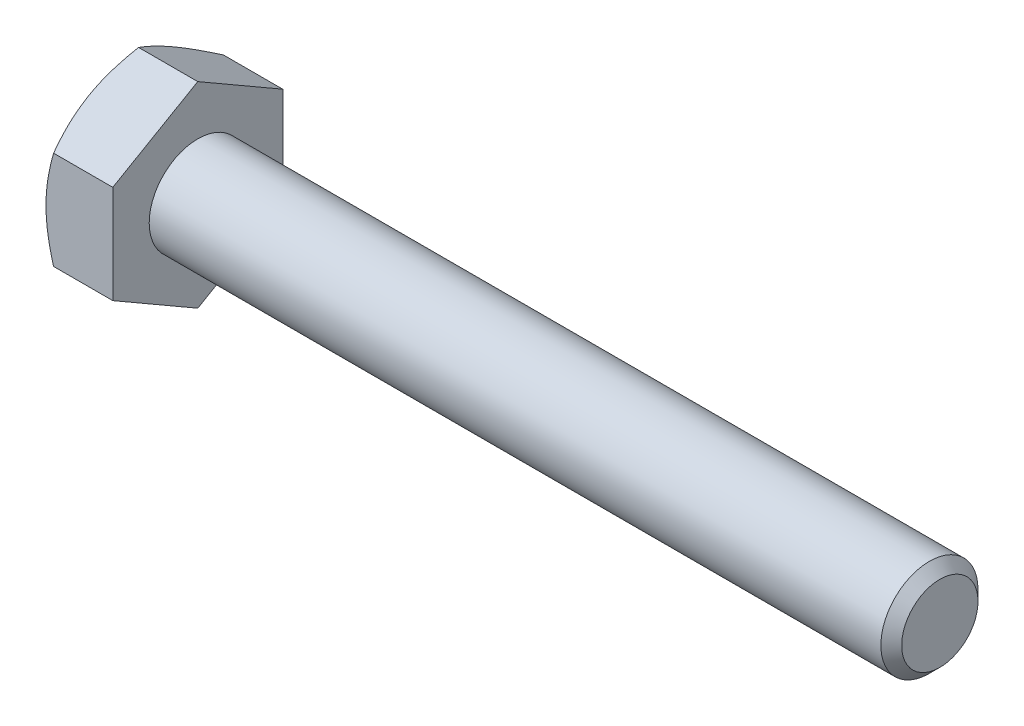
SolidWorks part; units mm, degrees
material "Alloy Steel"
ref_plane "Front Plane" through (0, 0, 0) normal (0, 0, 1) x (1, 0, 0)
ref_plane "Top Plane" through (0, 0, 0) normal (0, 1, 0) x (1, 0, 0)
ref_plane "Right Plane" through (0, 0, 0) normal (1, 0, 0) x (0, 0, -1)
sketch "Sketch1" plane through (0, 0, 0) normal (0, 0, 1) x (1, 0, 0)
  line L0 (-26.4398, 0) -> (26.4398, 0) construction
  line L1 (26.4398, 3.175) -> (26.4398, -3.175) construction
  line L2 (-22.0742, 5.5562) -> (-22.0742, -5.5562) construction
  line L3 (-26.4398, 5.5562) -> (-26.4398, -5.5562) construction
  point P9 (-22.0742, 0)
  point P10 (23.2648, -3.175)
  dimension "Screw Dia" = 6.35
  dimension "Hex" = 11.1125
  dimension "Head Ht" = 4.3656
  dimension "Screw Lenght" = 48.514
  dimension "D1" = 3.175
ref_plane "Plane2" through (26.4398, 0, 0) normal (1, 0, 0) x (0, 0, -1)
sketch "Sketch5" plane through (26.4398, 0, 0) normal (1, 0, 0) x (0, 0, -1)
  circle A0 centre (0, 0) radius 3.175
extrude "Boss-Extrude3" add sketch "Sketch5" against normal up to vertex (48.514 mm away) up to point (-22.0742, 0, 0)
sketch "Sketch9" plane through (26.4398, 0, 0) normal (1, 0, 0) x (0, 0, -1)
  circle A1 centre (0, 0) radius 3.175
  circle A2 centre (0, 0) radius 3.175
  dimension "D1" = 0
curve "Helix/Spiral1" [suppressed] pitch 0.9071 height 19.9571 turns 22 parameters "Pitch"=0.9071
chamfer "Chamfer1" distance 0.6804 angle 45 1 edges at (26.4398, 0, -3.175)
sketch "Sketch10" plane through (0, 0, 0) normal (0, 0, 1) x (1, 0, 0)
  line L0 (26.4398, 3.175) -> (26.78, 2.5858)
  line L1 (26.78, 2.5858) -> (26.8934, 2.5858)
  line L2 (26.8934, 2.5858) -> (27.2336, 3.175)
  line L3 (26.4398, 3.175) -> (27.2336, 3.175)
  line L4 (26.8367, 3.175) -> (26.8367, 2.5858) construction
  line L5 (26.6099, 2.8804) -> (27.0635, 2.8804) construction
  dimension "D1" = 60
  dimension "D2" = 0.1134
  dimension "D3" = 0.4536
sweep "Cut-Sweep1" [suppressed] cut profiles "Sketch10" path "Helix/Spiral1"
sketch "Sketch11" plane through (0, 0, 0) normal (0, 0, 1) x (1, 0, 0)
  line L0 (-22.0742, 3.175) -> (-22.0742, 0)
  line L1 (-22.0742, 0) -> (10.5648, 0)
  line L3 (10.5648, 0) -> (7.3898, 3.175)
  line L4 (-22.0742, 3.175) -> (7.3898, 3.175)
  dimension "D1" = 45
  dimension "MIn Thread" = 19.05
revolve "Revolve1" [suppressed] add sketch "Sketch11" angle 360 about L1
sketch "Sketch6" plane through (-22.0742, 0, 0) normal (-1, 0, 0) x (0, 0, 1)
  line L0 (0, 5.5562) -> (0, -5.5562) construction
  line L1 (5.5562, 3.2079) -> (0, 6.4158)
  line L2 (0, 6.4158) -> (-5.5562, 3.2079)
  line L3 (-5.5562, 3.2079) -> (-5.5562, -3.2079)
  line L4 (-5.5562, -3.2079) -> (0, -6.4158)
  line L5 (0, -6.4158) -> (5.5563, -3.2079)
  line L6 (5.5563, -3.2079) -> (5.5562, 3.2079)
  circle A0 centre (0, 0) radius 5.5562 construction
extrude "Boss-Extrude4" add sketch "Sketch6" along normal up to vertex (4.3656 mm away) up to point (-26.4398, -5.5562, 0)
sketch "Sketch7" plane through (-26.4398, 0, 0) normal (-1, 0, 0) x (0, 0, 1)
  circle A0 centre (0, 0) radius 5.5562 construction
  circle A1 centre (0, 0) radius 5.5562
sketch "Sketch8" plane through (-26.4398, 0, 0) normal (-1, 0, 0) x (0, 0, 1)
  circle A0 centre (0, 0) radius 5.5562 construction
  circle A1 centre (0, 0) radius 5.5562
extrude "Cut-Extrude3" cut sketch "Sketch8" against normal through all draft 60 flip side to cut
sketch "Sketch12" plane through (-26.4398, 0, 0) normal (-1, 0, 0) x (0, 0, 1)
  line L0 (0, 4.2783) -> (0, 2.3892) construction
  line L1 (0.1667, 4.2783) -> (0.1667, 2.3892)
  line L2 (-0.1667, 4.2783) -> (-0.1667, 2.3892)
  line L3 (0, 3.175) -> (0, -3.175) construction
  arc A0 (0.1667, 4.2783) -> (-0.1667, 4.2783) centre (0, 4.2783) ccw
  arc A1 (-0.1667, 2.3892) -> (0.1667, 2.3892) centre (0, 2.3892) ccw
  circle A3 centre (0, 0) radius 2.2225 construction
  circle A4 centre (0, 0) radius 4.445 construction
  point P2 (0, 3.3337)
  dimension "D1" = 4.445
  dimension "D3" = 8.89
  dimension "D2" = 0.3334
extrude "Cut-Extrude4" [suppressed] cut sketch "Sketch12" against normal blind 0.254
pattern_circular "CirPattern1" [suppressed] count 6 over 360 of bodies 116
equation "\"D2@Sketch10\" = \"Pitch@Helix/Spiral1\"*.125"
equation "\"D3@Sketch10\" = \"Pitch@Helix/Spiral1\"*.5"
equation "\"D3@Helix/Spiral1\" = \"MIn Thread@Sketch11\"+\"Pitch@Helix/Spiral1\""
equation "\"D1@Chamfer1\" = \"Pitch@Helix/Spiral1\"*.75"
equation "\"D1@Sketch12\" = \"Hex@Sketch1\"*.4"
equation "\"D3@Sketch12\" = \"Hex@Sketch1\"*.8"
equation "\"D2@Sketch12\" = \"Hex@Sketch1\"*.03"
equation "\"D1@Sketch1\" = \"Pitch@Helix/Spiral1\"*3.5"
